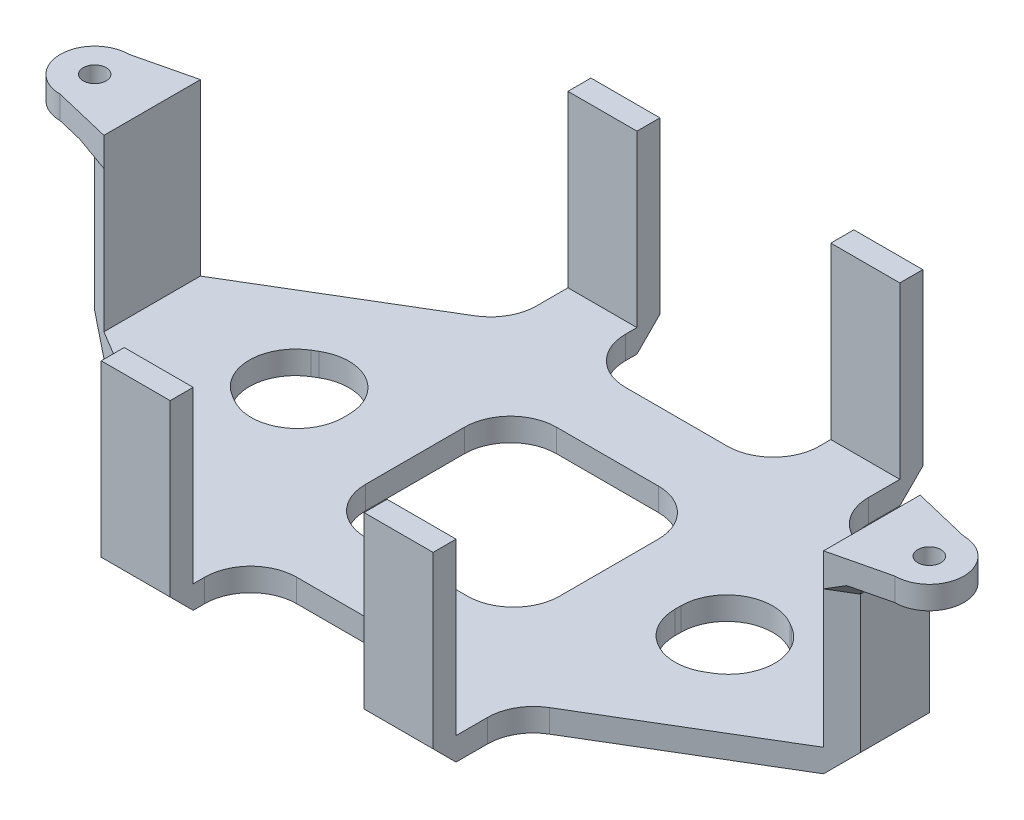
SolidWorks part; units mm, degrees
ref_plane "Front Plane" through (0, 0, 0) normal (0, 0, 1) x (1, 0, 0)
ref_plane "Top Plane" through (0, 0, 0) normal (0, 1, 0) x (1, 0, 0)
ref_plane "Right Plane" through (0, 0, 0) normal (1, 0, 0) x (0, 0, -1)
sketch "Sketch1" plane through (0, 0, 0) normal (0, 1, 0) x (1, 0, 0)
  line L0 (0, 0) -> (21.4207, 0) construction
  line L1 (79.502, 0) -> (79.502, 49.022) construction
  line L2 (79.502, 49.022) -> (58.0813, 49.022) construction
  line L3 (0, 49.022) -> (0, 0) construction
  line L4 (-2.54, 28.321) -> (21.4207, 42.672)
  line L5 (21.4207, 51.562) -> (29.0407, 51.562)
  line L6 (21.4207, 51.562) -> (21.4207, 42.672)
  line L7 (21.4207, -2.54) -> (29.0407, -2.54)
  line L8 (29.0407, 51.562) -> (29.0407, 42.672)
  line L9 (50.4613, 51.562) -> (58.0813, 51.562)
  line L10 (50.4613, 51.562) -> (50.4613, 42.672)
  line L11 (50.4613, -2.54) -> (58.0813, -2.54)
  line L12 (58.0813, 51.562) -> (58.0813, 42.672)
  line L13 (29.0407, 42.672) -> (50.4613, 42.672)
  line L14 (58.0813, 42.672) -> (82.042, 28.321)
  line L15 (82.042, 28.321) -> (82.042, 20.701)
  line L16 (82.042, 20.701) -> (58.0813, 6.35)
  line L17 (50.4613, 6.35) -> (29.0407, 6.35)
  line L18 (21.4207, 6.35) -> (-2.54, 20.701)
  line L19 (-2.54, 20.701) -> (-2.54, 28.321)
  line L20 (5.9287, 24.511) -> (21.4207, 33.7898)
  line L21 (29.0407, 35.052) -> (50.4613, 35.052)
  line L22 (58.0813, 33.7898) -> (73.5733, 24.511)
  line L23 (73.5733, 24.511) -> (73.5733, 24.511)
  line L24 (73.5733, 24.511) -> (58.0813, 15.2322)
  line L25 (50.4613, 13.97) -> (29.0407, 13.97)
  line L26 (21.4207, 15.2322) -> (5.9287, 24.511)
  line L27 (5.9287, 24.511) -> (5.9287, 24.511)
  line L28 (21.4207, 49.022) -> (0, 49.022) construction
  line L29 (21.4207, 42.672) -> (58.0813, 42.672) construction
  line L30 (23.5281, 35.052) -> (55.9739, 35.052) construction
  line L31 (23.5281, 13.97) -> (5.9287, 24.511) construction
  line L32 (58.0813, 6.35) -> (21.4207, 6.35) construction
  line L33 (29.0407, 0) -> (50.4613, 0) construction
  line L34 (55.9739, 13.97) -> (23.5281, 13.97) construction
  line L35 (5.9287, 24.511) -> (23.5281, 35.052) construction
  line L36 (73.5733, 24.511) -> (55.9739, 13.97) construction
  line L37 (55.9739, 35.052) -> (73.5733, 24.511) construction
  line L38 (50.4613, 49.022) -> (29.0407, 49.022) construction
  line L39 (58.0813, 0) -> (79.502, 0) construction
  line L40 (58.0813, 33.7898) -> (58.0813, 15.2322)
  line L41 (50.4613, 35.052) -> (50.4613, 13.97)
  line L42 (29.0407, 35.052) -> (29.0407, 13.97)
  line L43 (21.4207, 33.7898) -> (21.4207, 15.2322)
  line L44 (21.4207, 6.35) -> (21.4207, -2.54)
  line L45 (29.0407, 6.35) -> (29.0407, -2.54)
  line L46 (50.4613, 6.35) -> (50.4613, -2.54)
  line L47 (58.0813, 6.35) -> (58.0813, -2.54)
  point P15 (76.4457, 24.511)
  point P23 (79.502, 24.511)
  point P24 (82.042, 24.511)
  point P25 (-2.54, 24.511)
  dimension "D1" = 79.502
  dimension "D2" = 49.022
  dimension "D3" = 2.54
  dimension "D4" = 2.54
  dimension "D5" = 2.54
  dimension "D6" = 7.62
  dimension "D8" = 7.62
  dimension "D9" = 6.35
  dimension "D10" = 6.35
  dimension "D11" = 2.54
  dimension "D12" = 2.54
  dimension "D13" = 2.54
  dimension "D7" = 7.62
extrude "Boss-Extrude1" add sketch "Sketch1" along normal blind 2.54
sketch "Sketch2" plane through (0, 2.54, 0) normal (0, 1, 0) x (1, 0, 0)
  line L0 (29.0407, 42.672) -> (29.0407, 51.562) construction
  line L1 (21.4207, 51.562) -> (29.0407, 51.562)
  line L2 (21.4207, 51.562) -> (21.4207, 49.022)
  line L3 (21.4207, 49.022) -> (29.0407, 49.022)
  line L4 (29.0407, 51.562) -> (29.0407, 49.022)
  line L5 (58.0813, 42.672) -> (58.0813, 51.562) construction
  line L6 (50.4613, 51.562) -> (58.0813, 51.562)
  line L7 (50.4613, 51.562) -> (50.4613, 49.022)
  line L8 (50.4613, 49.022) -> (58.0813, 49.022)
  line L9 (58.0813, 51.562) -> (58.0813, 49.022)
  line L10 (21.4207, 6.35) -> (21.4207, -2.54) construction
  line L11 (29.0407, -2.54) -> (21.4207, -2.54)
  line L12 (29.0407, -2.54) -> (29.0407, 0)
  line L13 (29.0407, 0) -> (21.4207, 0)
  line L14 (21.4207, -2.54) -> (21.4207, 0)
  line L15 (58.0813, -2.54) -> (58.0813, 6.35) construction
  line L16 (50.4613, -2.54) -> (58.0813, -2.54)
  line L17 (50.4613, -2.54) -> (50.4613, 0)
  line L18 (50.4613, 0) -> (58.0813, 0)
  line L19 (58.0813, -2.54) -> (58.0813, 0)
  line L20 (-2.54, 20.701) -> (0, 19.1797)
  line L21 (-2.54, 20.701) -> (21.4207, 6.35) construction
  line L22 (0, 19.1797) -> (0, 29.8423)
  line L23 (21.4207, 42.672) -> (-2.54, 28.321) construction
  line L24 (0, 29.8423) -> (-2.54, 28.321)
  line L25 (-2.54, 28.321) -> (-2.54, 20.701)
  line L26 (82.042, 28.321) -> (79.502, 29.8423)
  line L27 (82.042, 28.321) -> (58.0813, 42.672) construction
  line L28 (79.502, 29.8423) -> (79.502, 19.1797)
  line L29 (58.0813, 6.35) -> (82.042, 20.701) construction
  line L30 (79.502, 19.1797) -> (82.042, 20.701)
  line L31 (82.042, 20.701) -> (82.042, 28.321)
  dimension "D1" = 2.54
  dimension "D2" = 2.54
  dimension "D3" = 2.54
  dimension "D4" = 2.54
extrude "Boss-Extrude2" add sketch "Sketch2" along normal blind 18.796
fillet "Fillet1" radius 5.08 18 edges at (58.0813, 1.27, -15.2322) (58.0813, 1.27, -33.7898) (73.5733, 1.27, -24.511) (29.0407, 1.27, -35.052) (29.0407, 1.27, -13.97) (50.4613, 1.27, -35.052) (21.4207, 1.27, -33.7898) (50.4613, 1.27, -13.97) (21.4207, 1.27, -15.2322) (5.9287, 1.27, -24.511) (58.0813, 1.27, -6.35) (58.0813, 1.27, -42.672) (29.0407, 1.27, -42.672) (50.4613, 1.27, -42.672) (21.4207, 1.27, -42.672) (21.4207, 1.27, -6.35) (50.4613, 1.27, -6.35) (29.0407, 1.27, -6.35)
chamfer "Chamfer1" distance 2.54 angle 45 6 edges at (82.042, 0, -24.511) (54.2713, 0, -51.562) (25.2307, 0, -51.562) (-2.54, 0, -24.511) (54.2713, 0, 2.54) (25.2307, 0, 2.54)
sketch "Sketch3" plane through (0, 21.336, 0) normal (0, 1, 0) x (1, 0, 0)
  line L0 (-6.35, 28.321) -> (0, 29.8423)
  line L1 (0, 29.8423) -> (0, 19.1797)
  line L2 (0, 19.1797) -> (-6.35, 20.701)
  line L3 (-2.54, 28.321) -> (-2.54, 20.701) construction
  line L4 (39.751, -988.57) -> (39.751, 49011.43) construction
  line L5 (34.1207, 13.97) -> (45.3813, 13.97) construction
  line L6 (79.502, 19.1797) -> (85.852, 20.701)
  line L7 (79.502, 29.8423) -> (79.502, 19.1797)
  line L8 (85.852, 28.321) -> (79.502, 29.8423)
  arc A0 (-6.35, 28.321) -> (-6.35, 20.701) centre (-6.35, 24.511) ccw
  circle A1 centre (-6.35, 24.511) radius 1.27
  circle A2 centre (85.852, 24.511) radius 1.27
  arc A3 (85.852, 28.321) -> (85.852, 20.701) centre (85.852, 24.511) cw
  point P17 (39.751, 13.97)
  point P23 (-2.54, 24.511)
  dimension "D1" = 2.54
  dimension "D2" = 2.54
  dimension "D3" = 3.81
extrude "Boss-Extrude3" add sketch "Sketch3" against normal blind 2.54
chamfer "Chamfer2" distance 0.635 angle 60 6 edges at (80.772, 18.796, -29.0817) (82.042, 18.796, -24.511) (80.772, 18.796, -19.9403) (-1.27, 18.796, -19.9403) (-2.54, 18.796, -24.511) (-1.27, 18.796, -29.0817) first distance on face at (85.852, 18.796, -25.781) first distance on face at (4.6888, 6.4589, -16.3714) first distance on face at (-2.54, 10.668, -24.511) first distance on face at (4.6888, 6.4589, -32.6506)
